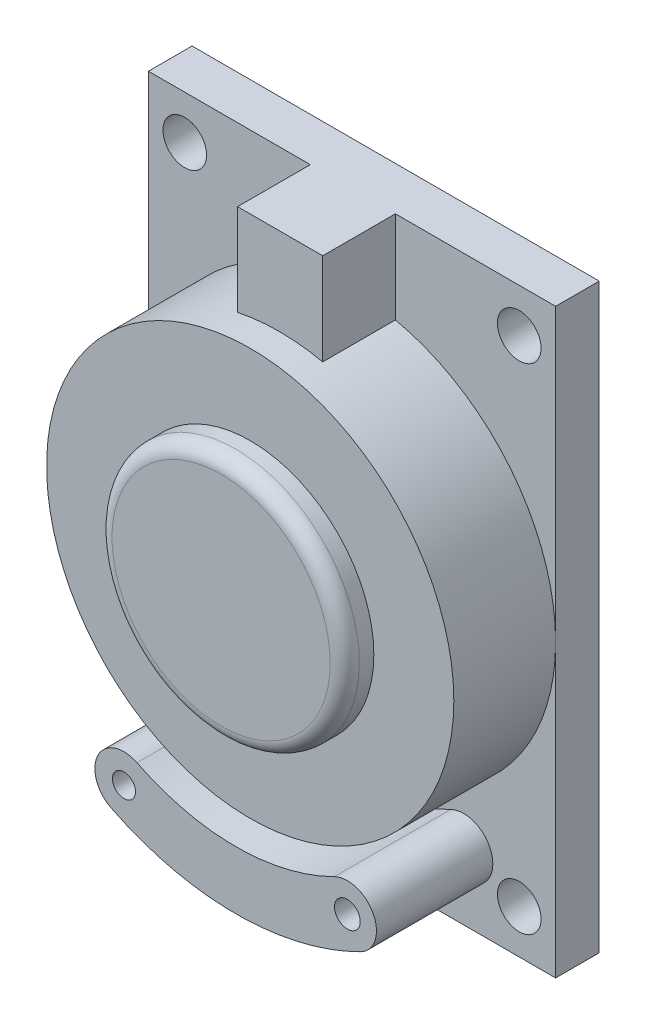
SolidWorks part; units mm, degrees
ref_plane "Front Plane" through (0, 0, 0) normal (0, 0, 1) x (1, 0, 0)
ref_plane "Top Plane" through (0, 0, 0) normal (0, 1, 0) x (1, 0, 0)
ref_plane "Right Plane" through (0, 0, 0) normal (1, 0, 0) x (0, 0, -1)
sketch "Sketch1" plane through (0, 0, 0) normal (0, 0, 1) x (1, 0, 0)
  line L1 (-14, -20) -> (14, -20)
  line L2 (-14, -20) -> (-14, 20)
  line L3 (-14, 20) -> (14, 20)
  line L4 (14, -20) -> (14, 20)
  line L5 (-14, -20) -> (14, 20) construction
  line L6 (-14, 20) -> (14, -20) construction
  point P0 (0, 0)
  dimension "D1" = 28
  dimension "D2" = 40
extrude "Boss-Extrude1" add sketch "Sketch1" along normal blind 3
sketch "Sketch2" plane through (0, 0, 3) normal (0, 0, 1) x (1, 0, 0)
  circle A0 centre (0, 0) radius 14
extrude "Boss-Extrude2" add sketch "Sketch2" along normal blind 7
sketch "Sketch3" plane through (0, 0, 10) normal (0, 0, 1) x (1, 0, 0)
  circle A0 centre (0, 0) radius 8.5
  dimension "D1" = 17
extrude "Boss-Extrude3" add sketch "Sketch3" along normal blind 2
fillet "Fillet1" radius 1 1 edges at (8.5, 0, 12)
sketch "Sketch4" plane through (0, 0, 3) normal (0, 0, 1) x (1, 0, 0)
  arc A0 (-7.6811, -15.3622) -> (7.6811, -15.3622) centre (0, 0) ccw construction
  arc A1 (-8.5755, -17.151) -> (8.5755, -17.151) centre (0, 0) ccw
  arc A2 (-6.7867, -13.5733) -> (6.7867, -13.5733) centre (0, 0) ccw
  arc A3 (-8.5755, -17.151) -> (-6.7867, -13.5733) centre (-7.6811, -15.3622) cw
  arc A4 (8.5755, -17.151) -> (6.7867, -13.5733) centre (7.6811, -15.3622) ccw
  circle A5 centre (7.6811, -15.3622) radius 0.8846
  circle A6 centre (-7.6811, -15.3622) radius 0.7936
  dimension "D1" = 2
  dimension "D2" = 2
extrude "Boss-Extrude4" add sketch "Sketch4" along normal blind 8
sketch "Sketch5" plane through (0, 0, 3) normal (0, 0, 1) x (1, 0, 0)
  line L0 (14, 20) -> (-14, 20) construction
  line L1 (-2.8674, 20) -> (2.9833, 20)
  line L2 (-2.8674, 20) -> (-2.8674, 12.8888)
  line L3 (-2.8674, 12.8888) -> (2.9833, 12.8888)
  line L4 (2.9833, 20) -> (2.9833, 12.8888)
extrude "Boss-Extrude5" add sketch "Sketch5" along normal blind 5
sketch "Sketch6" plane through (0, 0, 3) normal (0, 0, 1) x (1, 0, 0)
  line L1 (-11.5, -17) -> (11.5, -17) construction
  line L2 (-11.5, -17) -> (-11.5, 17) construction
  line L3 (-11.5, 17) -> (11.5, 17) construction
  line L4 (11.5, -17) -> (11.5, 17) construction
  line L5 (-11.5, -17) -> (11.5, 17) construction
  line L6 (-11.5, 17) -> (11.5, -17) construction
  circle A0 centre (-11.5, 17) radius 1.5
  circle A1 centre (11.5, 17) radius 1.5
  circle A2 centre (11.5, -17) radius 1.5
  circle A3 centre (-11.5, -17) radius 1.5
  point P0 (0, 0)
  dimension "D3" = 3
  dimension "D4" = 3
  dimension "D5" = 3
  dimension "D6" = 3
  dimension "D1" = 23
  dimension "D2" = 34
extrude "Cut-Extrude1" cut sketch "Sketch6" against normal blind 5
sketch "Sketch7" plane through (0, 0, 0) normal (0, 0, -1) x (-1, 0, 0)
  line L0 (0, -5) -> (0, 5) construction
  line L1 (-12, -5) -> (-12, 5)
  line L2 (12, -5) -> (12, 5)
  line L3 (0, 0) -> (14, 0) construction
  line L4 (14, 20) -> (14, -20) construction
  arc A0 (-12, -5) -> (12, -5) centre (0, -5) ccw
  arc A1 (12, 5) -> (-12, 5) centre (0, 5) ccw
  point P3 (0, 0)
  dimension "D2" = 12
  dimension "D1" = 10
extrude "Cut-Extrude2" cut sketch "Sketch7" against normal blind 1.5 draft 30
sketch "Sketch8" plane through (0, 0, 1.5) normal (0, 0, -1) x (-1, 0, 0)
  circle A0 centre (0, 0) radius 6.5
  dimension "D1" = 13
extrude "Boss-Extrude6" add sketch "Sketch8" along normal blind 1
fillet "Fillet2" radius 1 1 edges at (-6.5, 0, 0.5)
